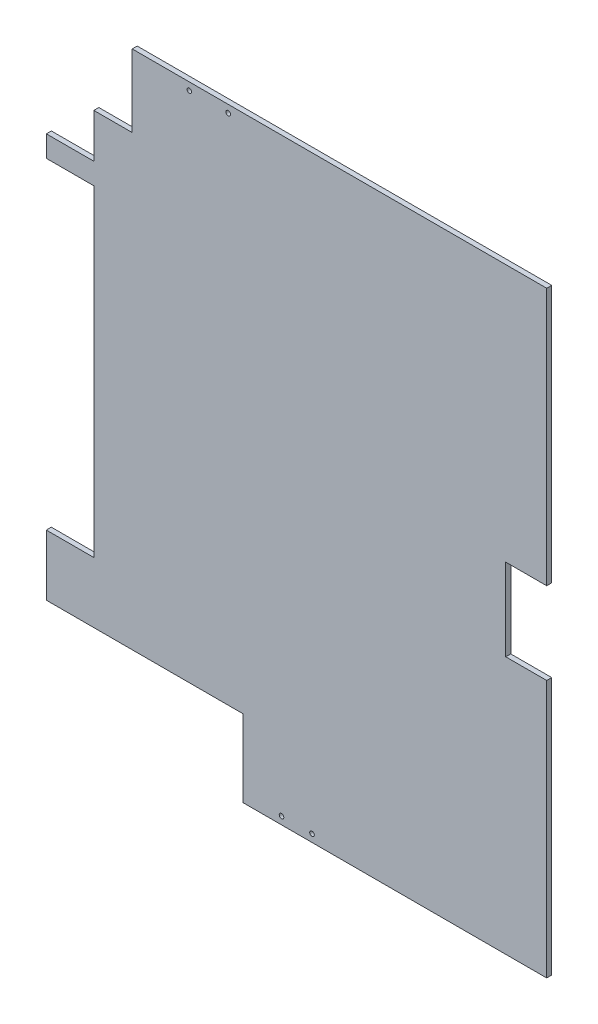
SolidWorks part; units mm, degrees
material "Balsa"
ref_plane "Front Plane" through (0, 0, 0) normal (0, 0, 1) x (1, 0, 0)
ref_plane "Top Plane" through (0, 0, 0) normal (0, 1, 0) x (1, 0, 0)
ref_plane "Right Plane" through (0, 0, 0) normal (1, 0, 0) x (0, 0, -1)
sketch "Sketch1" plane through (0, 0, 0) normal (0, 0, 1) x (1, 0, 0)
  line L0 (-5.7823, -13) -> (25.5, -13)
  line L2 (-5.7823, 1) -> (-5.7823, -13)
  line L5 (24.5, -14) -> (-24.5, -14) construction
  line L6 (323.7481, -265) -> (323.7481, 30)
  line L7 (-5.8246, -265) -> (65.6329, -265)
  line L8 (-5.8246, -265) -> (-5.8246, -225)
  line L11 (-5.8246, -265) -> (65.6329, -225) construction
  line L12 (-5.8246, -225) -> (65.6329, -265) construction
  line L15 (323.7481, -265) -> (25.5, -265)
  line L16 (25.5, 1) -> (25.5, -265)
  line L17 (-5.8246, -225) -> (25.5, -225)
  line L18 (-24.5, -224) -> (24.5, -224) construction
  line L19 (-5.7823, 1) -> (25.5, 1)
  line L20 (24.5, -224) -> (24.5, -14) construction
  line L21 (-85.1981, 31) -> (50.7481, 31) construction
  line L23 (25.5, 1) -> (25.5, 30)
  line L24 (25.5, 30) -> (323.7481, 30)
  line L27 (277.3251, 57) -> (277.3251, -295) construction
  line L28 (26.2777, -266) -> (-26.2882, -266) construction
  line L30 (-63.4467, 81) -> (255.5737, 81) construction
  line L31 (50.7481, 30) -> (323.7481, 30)
  line L32 (50.7481, 30) -> (50.7481, 77.7)
  line L33 (50.7481, 77.7) -> (323.7481, 77.7)
  line L34 (323.7481, 30) -> (323.7481, 77.7)
  line L35 (50.7481, 30) -> (323.7481, 77.7) construction
  line L36 (50.7481, 77.7) -> (323.7481, 30) construction
  line L37 (255.5737, -319) -> (-63.4467, -319) construction
  line L38 (323.7481, -265) -> (123.7481, -265)
  line L39 (323.7481, -265) -> (323.7481, -315.7)
  line L40 (323.7481, -315.7) -> (123.7481, -315.7)
  line L41 (123.7481, -265) -> (123.7481, -315.7)
  line L42 (323.7481, -265) -> (123.7481, -315.7) construction
  line L43 (323.7481, -315.7) -> (123.7481, -265) construction
  line L44 (50.7481, 31) -> (50.7481, -269) construction
  point P4 (32.4695, -6)
  point P10 (29.9042, -245)
  point P15 (48.1318, -132)
  point P24 (48.1318, 15.5)
  point P36 (187.2481, 53.85)
  point P42 (223.7481, -290.35)
  dimension "D1" = 1
  dimension "D2" = 1
  dimension "D3" = 1
  dimension "D4" = 1
  dimension "D5" = 1
  dimension "D6" = 31.3246
  dimension "D7" = 273
  dimension "D8" = 3.3
  dimension "D9" = 200
  dimension "D10" = 3.3
extrude "Boss-Extrude1" add sketch "Sketch1" along normal blind 3.3 contours L24 L23 L16 L7 L15 L6 | L19 L2 L0 L16 | L17 L8 L7 L16 | L24 L34 L33 L32 | L15 L41 L40 L39 region at (9.8589, -6, 0) region at (174.6241, -117.5, 0) region at (9.8377, -245, 0) region at (187.2481, 53.85, 0) region at (223.7481, -290.35, 0)
sketch "Sketch2" plane through (0, 0, 0) normal (0, 0, -1) x (-1, 0, 0)
  circle A0 centre (-113.9984, 72.7) radius 1.5
  circle A1 centre (-88.397, 72.7) radius 1.5
  circle A2 centre (-169.1689, -310.7) radius 1.5
  circle A3 centre (-149.0844, -310.7) radius 1.5
  dimension "D1" = 3
  dimension "D2" = 3
  dimension "D3" = 3
  dimension "D4" = 3
extrude "Cut-Extrude1" cut sketch "Sketch2" against normal through all
sketch "Sketch3" plane through (119.3915, 0, 256.0358) normal (0.4226, 0, 0.9063) x (0.9063, 0, -0.4226)
  line L1 (293.4595, -146) -> (268.9595, -146)
  line L2 (293.4595, -146) -> (293.4595, -92)
  line L3 (293.4595, -92) -> (268.9595, -92)
  line L4 (268.9595, -146) -> (268.9595, -92)
  line L5 (293.4595, -146) -> (268.9595, -92) construction
  line L6 (293.4595, -92) -> (268.9595, -146) construction
  point P4 (281.2095, -119)
extrude "Cut-Extrude2" cut sketch "Sketch3" against normal through all both and the other way through all
sketch "Sketch4" plane through (0, 0, 0) normal (0, 0, -1) x (-1, 0, 0)
  line L1 (-323.7481, -92) -> (-296.7639, -92)
  line L2 (-323.7481, -92) -> (-323.7481, -146)
  line L3 (-323.7481, -146) -> (-296.7639, -146)
  line L4 (-296.7639, -92) -> (-296.7639, -146)
  line L5 (-323.7481, -92) -> (-296.7639, -146) construction
  line L6 (-323.7481, -146) -> (-296.7639, -92) construction
  point P4 (-310.256, -119)
extrude "Cut-Extrude3" cut sketch "Sketch4" against normal blind 10
